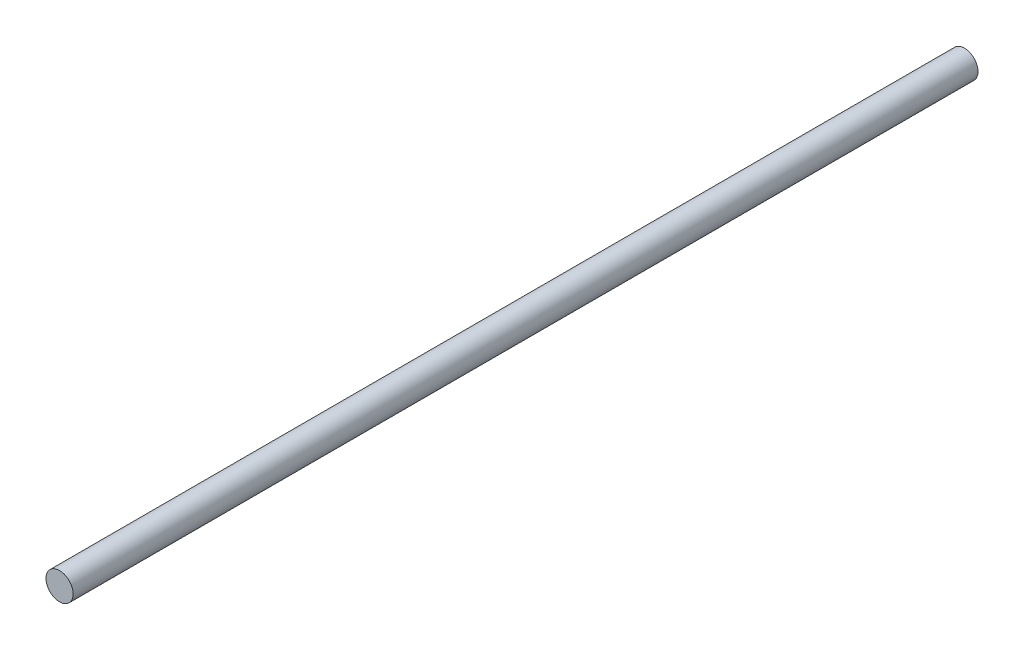
SolidWorks part; units mm, degrees
ref_plane "Front Plane" through (0, 0, 0) normal (0, 0, 1) x (1, 0, 0)
ref_plane "Top Plane" through (0, 0, 0) normal (0, 1, 0) x (1, 0, 0)
ref_plane "Right Plane" through (0, 0, 0) normal (1, 0, 0) x (0, 0, -1)
sketch "Sketch1" plane through (0, 0, 0) normal (0, 0, 1) x (1, 0, 0)
  circle A0 centre (0, 0.6456) radius 3
  dimension "D1" = 6
extrude "Boss-Extrude1" add sketch "Sketch1" along normal blind 100 and the other way blind 100
